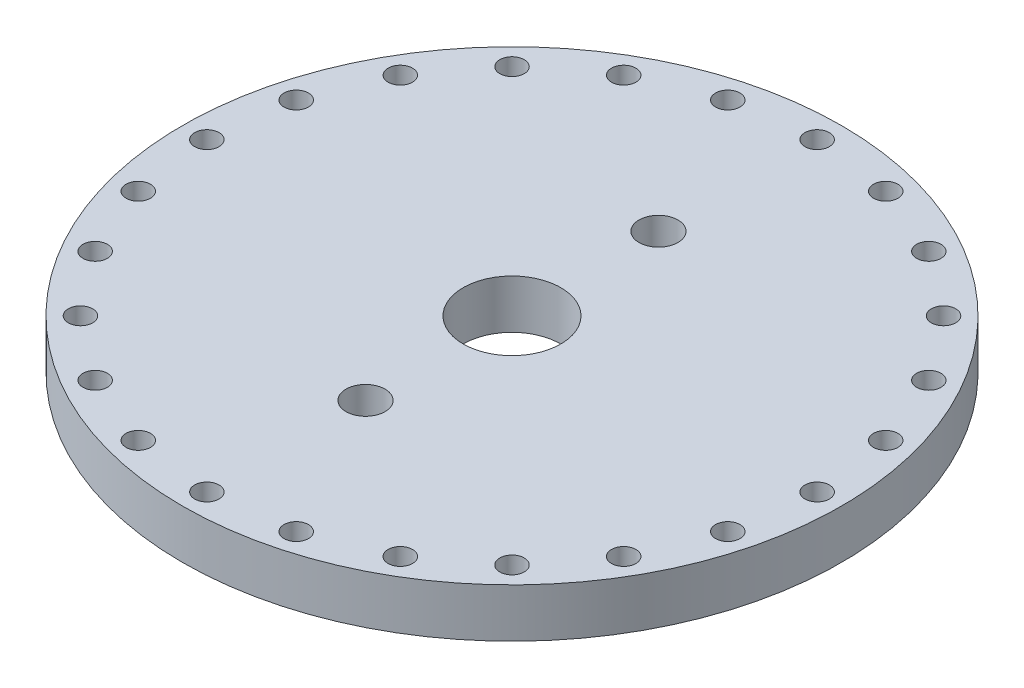
SolidWorks part; units mm, degrees
material "Brass"
ref_plane "Front Plane" through (0, 0, 0) normal (0, 0, 1) x (1, 0, 0)
ref_plane "Top Plane" through (0, 0, 0) normal (0, 1, 0) x (1, 0, 0)
ref_plane "Right Plane" through (0, 0, 0) normal (1, 0, 0) x (0, 0, -1)
sketch "Sketch5" plane through (0, 0, 0) normal (0, 1, 0) x (1, 0, 0)
  line L0 (87.3464, 51.4964) -> (89.0397, 50.8872)
  line L1 (89.0397, 50.8872) -> (90.7249, 50.062)
  line L2 (90.7249, 50.062) -> (90.7249, 49.095)
  line L3 (90.7249, 49.095) -> (89.0397, 48.2698)
  line L4 (89.0397, 48.2698) -> (87.3464, 47.6606)
  line L5 (87.3464, 47.6606) -> (87.2693, 46.4828)
  line L6 (87.2693, 46.4828) -> (88.8685, 45.6578)
  line L7 (88.8685, 45.6578) -> (90.4317, 44.6196)
  line L8 (90.4317, 44.6196) -> (90.3054, 43.6609)
  line L9 (90.3054, 43.6609) -> (88.5268, 43.0627)
  line L10 (88.5268, 43.0627) -> (86.7686, 42.6797)
  line L11 (86.7686, 42.6797) -> (86.5383, 41.5221)
  line L12 (86.5383, 41.5221) -> (88.0162, 40.4955)
  line L13 (88.0162, 40.4955) -> (89.4304, 39.2621)
  line L14 (89.4304, 39.2621) -> (89.1801, 38.328)
  line L15 (89.1801, 38.328) -> (87.3386, 37.9672)
  line L16 (87.3386, 37.9672) -> (85.5454, 37.8169)
  line L17 (85.5454, 37.8169) -> (85.1661, 36.6994)
  line L18 (85.1661, 36.6994) -> (86.4974, 35.4884)
  line L19 (86.4974, 35.4884) -> (87.7385, 34.0811)
  line L20 (87.7385, 34.0811) -> (87.3685, 33.1877)
  line L21 (87.3685, 33.1877) -> (85.4956, 33.0702)
  line L22 (85.4956, 33.0702) -> (83.6981, 33.1553)
  line L23 (83.6981, 33.1553) -> (83.1762, 32.0968)
  line L24 (83.1762, 32.0968) -> (84.3379, 30.7226)
  line L25 (84.3379, 30.7226) -> (85.3848, 29.1653)
  line L26 (85.3848, 29.1653) -> (84.9013, 28.3278)
  line L27 (84.9013, 28.3278) -> (83.0292, 28.4557)
  line L28 (83.0292, 28.4557) -> (81.2581, 28.7747)
  line L29 (81.2581, 28.7747) -> (80.6024, 27.7935)
  line L30 (80.6024, 27.7935) -> (81.575, 26.2794)
  line L31 (81.575, 26.2794) -> (82.4096, 24.5987)
  line L32 (82.4096, 24.5987) -> (81.821, 23.8315)
  line L33 (81.821, 23.8315) -> (79.9815, 24.2028)
  line L34 (79.9815, 24.2028) -> (78.2673, 24.7502)
  line L35 (78.2673, 24.7502) -> (77.4891, 23.8628)
  line L36 (77.4891, 23.8628) -> (78.2556, 22.2348)
  line L37 (78.2556, 22.2348) -> (78.8638, 20.4595)
  line L38 (78.8638, 20.4595) -> (78.18, 19.7757)
  line L39 (78.18, 19.7757) -> (76.4047, 20.3839)
  line L40 (76.4047, 20.3839) -> (74.7767, 21.1504)
  line L41 (74.7767, 21.1504) -> (73.8893, 20.3722)
  line L42 (73.8893, 20.3722) -> (74.4368, 18.658)
  line L43 (74.4368, 18.658) -> (74.808, 16.8186)
  line L44 (74.808, 16.8186) -> (74.0408, 16.2299)
  line L45 (74.0408, 16.2299) -> (72.3602, 17.0645)
  line L46 (72.3602, 17.0645) -> (70.846, 18.0371)
  line L47 (70.846, 18.0371) -> (69.8648, 17.3814)
  line L48 (69.8648, 17.3814) -> (70.1838, 15.6104)
  line L49 (70.1838, 15.6104) -> (70.3117, 13.7382)
  line L50 (70.3117, 13.7382) -> (69.4742, 13.2547)
  line L51 (69.4742, 13.2547) -> (67.9169, 14.3016)
  line L52 (67.9169, 14.3016) -> (66.5427, 15.4634)
  line L53 (66.5427, 15.4634) -> (65.4842, 14.9415)
  line L54 (65.4842, 14.9415) -> (65.5693, 13.1439)
  line L55 (65.5693, 13.1439) -> (65.4518, 11.271)
  line L56 (65.4518, 11.271) -> (64.5584, 10.901)
  line L57 (64.5584, 10.901) -> (63.1511, 12.1422)
  line L58 (63.1511, 12.1422) -> (61.9401, 13.4734)
  line L59 (61.9401, 13.4734) -> (60.8226, 13.0941)
  line L60 (60.8226, 13.0941) -> (60.6724, 11.3009)
  line L61 (60.6724, 11.3009) -> (60.3115, 9.4594)
  line L62 (60.3115, 9.4594) -> (59.3774, 9.2091)
  line L63 (59.3774, 9.2091) -> (58.144, 10.6233)
  line L64 (58.144, 10.6233) -> (57.1174, 12.1012)
  line L65 (57.1174, 12.1012) -> (55.9598, 11.8709)
  line L66 (55.9598, 11.8709) -> (55.5768, 10.1127)
  line L67 (55.5768, 10.1127) -> (54.9786, 8.3341)
  line L68 (54.9786, 8.3341) -> (54.0199, 8.2078)
  line L69 (54.0199, 8.2078) -> (52.9817, 9.771)
  line L70 (52.9817, 9.771) -> (52.1567, 11.3702)
  line L71 (52.1567, 11.3702) -> (50.979, 11.2931)
  line L72 (50.979, 11.2931) -> (50.3698, 9.5998)
  line L73 (50.3698, 9.5998) -> (49.5446, 7.9146)
  line L74 (49.5446, 7.9146) -> (48.5775, 7.9146)
  line L75 (48.5775, 7.9146) -> (47.7523, 9.5998)
  line L76 (47.7523, 9.5998) -> (47.1431, 11.2931)
  line L77 (47.1431, 11.2931) -> (45.9654, 11.3702)
  line L78 (45.9654, 11.3702) -> (45.1403, 9.771)
  line L79 (45.1403, 9.771) -> (44.1021, 8.2078)
  line L80 (44.1021, 8.2078) -> (43.1434, 8.3341)
  line L81 (43.1434, 8.3341) -> (42.5452, 10.1127)
  line L82 (42.5452, 10.1127) -> (42.1622, 11.8709)
  line L83 (42.1622, 11.8709) -> (41.0046, 12.1012)
  line L84 (41.0046, 12.1012) -> (39.978, 10.6233)
  line L85 (39.978, 10.6233) -> (38.7447, 9.2091)
  line L86 (38.7447, 9.2091) -> (37.8106, 9.4594)
  line L87 (37.8106, 9.4594) -> (37.4497, 11.3009)
  line L88 (37.4497, 11.3009) -> (37.2994, 13.0941)
  line L89 (37.2994, 13.0941) -> (36.1819, 13.4734)
  line L90 (36.1819, 13.4734) -> (34.9709, 12.1422)
  line L91 (34.9709, 12.1422) -> (33.5636, 10.901)
  line L92 (33.5636, 10.901) -> (32.6702, 11.271)
  line L93 (32.6702, 11.271) -> (32.5527, 13.1439)
  line L94 (32.5527, 13.1439) -> (32.6378, 14.9415)
  line L95 (32.6378, 14.9415) -> (31.5793, 15.4634)
  line L96 (31.5793, 15.4634) -> (30.2051, 14.3016)
  line L97 (30.2051, 14.3016) -> (28.6478, 13.2547)
  line L98 (28.6478, 13.2547) -> (27.8103, 13.7382)
  line L99 (27.8103, 13.7382) -> (27.9382, 15.6104)
  line L100 (27.9382, 15.6104) -> (28.2572, 17.3814)
  line L101 (28.2572, 17.3814) -> (27.276, 18.0371)
  line L102 (27.276, 18.0371) -> (25.7619, 17.0645)
  line L103 (25.7619, 17.0645) -> (24.0812, 16.2299)
  line L104 (24.0812, 16.2299) -> (23.314, 16.8186)
  line L105 (23.314, 16.8186) -> (23.6853, 18.658)
  line L106 (23.6853, 18.658) -> (24.2327, 20.3722)
  line L107 (24.2327, 20.3722) -> (23.3453, 21.1504)
  line L108 (23.3453, 21.1504) -> (21.7173, 20.3839)
  line L109 (21.7173, 20.3839) -> (19.9421, 19.7757)
  line L110 (19.9421, 19.7757) -> (19.2582, 20.4595)
  line L111 (19.2582, 20.4595) -> (19.8664, 22.2348)
  line L112 (19.8664, 22.2348) -> (20.6329, 23.8628)
  line L113 (20.6329, 23.8628) -> (19.8547, 24.7502)
  line L114 (19.8547, 24.7502) -> (18.1405, 24.2028)
  line L115 (18.1405, 24.2028) -> (16.3011, 23.8315)
  line L116 (16.3011, 23.8315) -> (15.7124, 24.5987)
  line L117 (15.7124, 24.5987) -> (16.547, 26.2794)
  line L118 (16.547, 26.2794) -> (17.5196, 27.7935)
  line L119 (17.5196, 27.7935) -> (16.8639, 28.7747)
  line L120 (16.8639, 28.7747) -> (15.0929, 28.4557)
  line L121 (15.0929, 28.4557) -> (13.2207, 28.3278)
  line L122 (13.2207, 28.3278) -> (12.7372, 29.1653)
  line L123 (12.7372, 29.1653) -> (13.7841, 30.7226)
  line L124 (13.7841, 30.7226) -> (14.9459, 32.0968)
  line L125 (14.9459, 32.0968) -> (14.424, 33.1553)
  line L126 (14.424, 33.1553) -> (12.6264, 33.0702)
  line L127 (12.6264, 33.0702) -> (10.7535, 33.1877)
  line L128 (10.7535, 33.1877) -> (10.3835, 34.0811)
  line L129 (10.3835, 34.0811) -> (11.6247, 35.4884)
  line L130 (11.6247, 35.4884) -> (12.9559, 36.6994)
  line L131 (12.9559, 36.6994) -> (12.5766, 37.8169)
  line L132 (12.5766, 37.8169) -> (10.7834, 37.9672)
  line L133 (10.7834, 37.9672) -> (8.9419, 38.328)
  line L134 (8.9419, 38.328) -> (8.6916, 39.2621)
  line L135 (8.6916, 39.2621) -> (10.1058, 40.4955)
  line L136 (10.1058, 40.4955) -> (11.5837, 41.5221)
  line L137 (11.5837, 41.5221) -> (11.3534, 42.6797)
  line L138 (11.3534, 42.6797) -> (9.5952, 43.0627)
  line L139 (9.5952, 43.0627) -> (7.8167, 43.6609)
  line L140 (7.8167, 43.6609) -> (7.6903, 44.6196)
  line L141 (7.6903, 44.6196) -> (9.2536, 45.6578)
  line L142 (9.2536, 45.6578) -> (10.8528, 46.4828)
  line L143 (10.8528, 46.4828) -> (10.7757, 47.6606)
  line L144 (10.7757, 47.6606) -> (9.0823, 48.2698)
  line L145 (9.0823, 48.2698) -> (7.3971, 49.095)
  line L146 (7.3971, 49.095) -> (7.3971, 50.062)
  line L147 (7.3971, 50.062) -> (9.0823, 50.8872)
  line L148 (9.0823, 50.8872) -> (10.7757, 51.4964)
  line L149 (10.7757, 51.4964) -> (10.8528, 52.6742)
  line L150 (10.8528, 52.6742) -> (9.2536, 53.4992)
  line L151 (9.2536, 53.4992) -> (7.6903, 54.5374)
  line L152 (7.6903, 54.5374) -> (7.8167, 55.4961)
  line L153 (7.8167, 55.4961) -> (9.5952, 56.0943)
  line L154 (9.5952, 56.0943) -> (11.3534, 56.4773)
  line L155 (11.3534, 56.4773) -> (11.5837, 57.6349)
  line L156 (11.5837, 57.6349) -> (10.1058, 58.6615)
  line L157 (10.1058, 58.6615) -> (8.6916, 59.8949)
  line L158 (8.6916, 59.8949) -> (8.9419, 60.829)
  line L159 (8.9419, 60.829) -> (10.7834, 61.1898)
  line L160 (10.7834, 61.1898) -> (12.5766, 61.3401)
  line L161 (12.5766, 61.3401) -> (12.9559, 62.4576)
  line L162 (12.9559, 62.4576) -> (11.6247, 63.6686)
  line L163 (11.6247, 63.6686) -> (10.3835, 65.0759)
  line L164 (10.3835, 65.0759) -> (10.7535, 65.9693)
  line L165 (10.7535, 65.9693) -> (12.6264, 66.0868)
  line L166 (12.6264, 66.0868) -> (14.424, 66.0017)
  line L167 (14.424, 66.0017) -> (14.9459, 67.0602)
  line L168 (14.9459, 67.0602) -> (13.7841, 68.4344)
  line L169 (13.7841, 68.4344) -> (12.7372, 69.9917)
  line L170 (12.7372, 69.9917) -> (13.2207, 70.8292)
  line L171 (13.2207, 70.8292) -> (15.0929, 70.7013)
  line L172 (15.0929, 70.7013) -> (16.8639, 70.3823)
  line L173 (16.8639, 70.3823) -> (17.5196, 71.3635)
  line L174 (17.5196, 71.3635) -> (16.547, 72.8776)
  line L175 (16.547, 72.8776) -> (15.7124, 74.5583)
  line L176 (15.7124, 74.5583) -> (16.3011, 75.3255)
  line L177 (16.3011, 75.3255) -> (18.1405, 74.9542)
  line L178 (18.1405, 74.9542) -> (19.8547, 74.4068)
  line L179 (19.8547, 74.4068) -> (20.6329, 75.2942)
  line L180 (20.6329, 75.2942) -> (19.8664, 76.9222)
  line L181 (19.8664, 76.9222) -> (19.2582, 78.6975)
  line L182 (19.2582, 78.6975) -> (19.9421, 79.3813)
  line L183 (19.9421, 79.3813) -> (21.7173, 78.7731)
  line L184 (21.7173, 78.7731) -> (23.3453, 78.0066)
  line L185 (23.3453, 78.0066) -> (24.2327, 78.7848)
  line L186 (24.2327, 78.7848) -> (23.6853, 80.499)
  line L187 (23.6853, 80.499) -> (23.314, 82.3384)
  line L188 (23.314, 82.3384) -> (24.0812, 82.9271)
  line L189 (24.0812, 82.9271) -> (25.7619, 82.0925)
  line L190 (25.7619, 82.0925) -> (27.276, 81.1199)
  line L191 (27.276, 81.1199) -> (28.2572, 81.7756)
  line L192 (28.2572, 81.7756) -> (27.9382, 83.5466)
  line L193 (27.9382, 83.5466) -> (27.8103, 85.4188)
  line L194 (27.8103, 85.4188) -> (28.6478, 85.9023)
  line L195 (28.6478, 85.9023) -> (30.2051, 84.8554)
  line L196 (30.2051, 84.8554) -> (31.5793, 83.6936)
  line L197 (31.5793, 83.6936) -> (32.6378, 84.2155)
  line L198 (32.6378, 84.2155) -> (32.5527, 86.0131)
  line L199 (32.5527, 86.0131) -> (32.6702, 87.886)
  line L200 (32.6702, 87.886) -> (33.5636, 88.256)
  line L201 (33.5636, 88.256) -> (34.9709, 87.0148)
  line L202 (34.9709, 87.0148) -> (36.1819, 85.6836)
  line L203 (36.1819, 85.6836) -> (37.2994, 86.0629)
  line L204 (37.2994, 86.0629) -> (37.4497, 87.8561)
  line L205 (37.4497, 87.8561) -> (37.8106, 89.6976)
  line L206 (37.8106, 89.6976) -> (38.7447, 89.9479)
  line L207 (38.7447, 89.9479) -> (39.978, 88.5337)
  line L208 (39.978, 88.5337) -> (41.0046, 87.0558)
  line L209 (41.0046, 87.0558) -> (42.1622, 87.2861)
  line L210 (42.1622, 87.2861) -> (42.5452, 89.0443)
  line L211 (42.5452, 89.0443) -> (43.1434, 90.8228)
  line L212 (43.1434, 90.8228) -> (44.1021, 90.9492)
  line L213 (44.1021, 90.9492) -> (45.1403, 89.386)
  line L214 (45.1403, 89.386) -> (45.9654, 87.7868)
  line L215 (45.9654, 87.7868) -> (47.1431, 87.8639)
  line L216 (47.1431, 87.8639) -> (47.7523, 89.5572)
  line L217 (47.7523, 89.5572) -> (48.5775, 91.2424)
  line L218 (48.5775, 91.2424) -> (49.5446, 91.2424)
  line L219 (49.5446, 91.2424) -> (50.3698, 89.5572)
  line L220 (50.3698, 89.5572) -> (50.979, 87.8639)
  line L221 (50.979, 87.8639) -> (52.1567, 87.7868)
  line L222 (52.1567, 87.7868) -> (52.9817, 89.386)
  line L223 (52.9817, 89.386) -> (54.0199, 90.9492)
  line L224 (54.0199, 90.9492) -> (54.9786, 90.8228)
  line L225 (54.9786, 90.8228) -> (55.5768, 89.0443)
  line L226 (55.5768, 89.0443) -> (55.9598, 87.2861)
  line L227 (55.9598, 87.2861) -> (57.1174, 87.0558)
  line L228 (57.1174, 87.0558) -> (58.144, 88.5337)
  line L229 (58.144, 88.5337) -> (59.3774, 89.9479)
  line L230 (59.3774, 89.9479) -> (60.3115, 89.6976)
  line L231 (60.3115, 89.6976) -> (60.6724, 87.8561)
  line L232 (60.6724, 87.8561) -> (60.8226, 86.0629)
  line L233 (60.8226, 86.0629) -> (61.9401, 85.6836)
  line L234 (61.9401, 85.6836) -> (63.1511, 87.0148)
  line L235 (63.1511, 87.0148) -> (64.5584, 88.256)
  line L236 (64.5584, 88.256) -> (65.4518, 87.886)
  line L237 (65.4518, 87.886) -> (65.5693, 86.0131)
  line L238 (65.5693, 86.0131) -> (65.4842, 84.2155)
  line L239 (65.4842, 84.2155) -> (66.5427, 83.6936)
  line L240 (66.5427, 83.6936) -> (67.9169, 84.8554)
  line L241 (67.9169, 84.8554) -> (69.4742, 85.9023)
  line L242 (69.4742, 85.9023) -> (70.3117, 85.4188)
  line L243 (70.3117, 85.4188) -> (70.1838, 83.5466)
  line L244 (70.1838, 83.5466) -> (69.8648, 81.7756)
  line L245 (69.8648, 81.7756) -> (70.846, 81.1199)
  line L246 (70.846, 81.1199) -> (72.3602, 82.0925)
  line L247 (72.3602, 82.0925) -> (74.0408, 82.9271)
  line L248 (74.0408, 82.9271) -> (74.808, 82.3384)
  line L249 (74.808, 82.3384) -> (74.4368, 80.499)
  line L250 (74.4368, 80.499) -> (73.8893, 78.7848)
  line L251 (73.8893, 78.7848) -> (74.7767, 78.0066)
  line L252 (74.7767, 78.0066) -> (76.4047, 78.7731)
  line L253 (76.4047, 78.7731) -> (78.18, 79.3813)
  line L254 (78.18, 79.3813) -> (78.8638, 78.6975)
  line L255 (78.8638, 78.6975) -> (78.2556, 76.9222)
  line L256 (78.2556, 76.9222) -> (77.4891, 75.2942)
  line L257 (77.4891, 75.2942) -> (78.2673, 74.4068)
  line L258 (78.2673, 74.4068) -> (79.9815, 74.9542)
  line L259 (79.9815, 74.9542) -> (81.821, 75.3255)
  line L260 (81.821, 75.3255) -> (82.4096, 74.5583)
  line L261 (82.4096, 74.5583) -> (81.575, 72.8776)
  line L262 (81.575, 72.8776) -> (80.6024, 71.3635)
  line L263 (80.6024, 71.3635) -> (81.2581, 70.3823)
  line L264 (81.2581, 70.3823) -> (83.0292, 70.7013)
  line L265 (83.0292, 70.7013) -> (84.9013, 70.8292)
  line L266 (84.9013, 70.8292) -> (85.3848, 69.9917)
  line L267 (85.3848, 69.9917) -> (84.3379, 68.4344)
  line L268 (84.3379, 68.4344) -> (83.1762, 67.0602)
  line L269 (83.1762, 67.0602) -> (83.6981, 66.0017)
  line L270 (83.6981, 66.0017) -> (85.4956, 66.0868)
  line L271 (85.4956, 66.0868) -> (87.3685, 65.9693)
  line L272 (87.3685, 65.9693) -> (87.7385, 65.0759)
  line L273 (87.7385, 65.0759) -> (86.4974, 63.6686)
  line L274 (86.4974, 63.6686) -> (85.1661, 62.4576)
  line L275 (85.1661, 62.4576) -> (85.5454, 61.3401)
  line L276 (85.5454, 61.3401) -> (87.3386, 61.1898)
  line L277 (87.3386, 61.1898) -> (89.1801, 60.829)
  line L278 (89.1801, 60.829) -> (89.4304, 59.8949)
  line L279 (89.4304, 59.8949) -> (88.0162, 58.6615)
  line L280 (88.0162, 58.6615) -> (86.5383, 57.6349)
  line L281 (86.5383, 57.6349) -> (86.7686, 56.4773)
  line L282 (86.7686, 56.4773) -> (88.5268, 56.0943)
  line L283 (88.5268, 56.0943) -> (90.3054, 55.4961)
  line L284 (90.3054, 55.4961) -> (90.4317, 54.5374)
  line L285 (90.4317, 54.5374) -> (88.8685, 53.4992)
  line L286 (88.8685, 53.4992) -> (87.2693, 52.6742)
  line L287 (87.2693, 52.6742) -> (87.3464, 51.4964)
  line L288 (49.061, 91.2424) -> (49.061, 7.9146) construction
  line L289 (7.3971, 49.5785) -> (90.7249, 49.5785) construction
  point P292 (49.061, 49.5785)
sketch "Sketch6" plane through (0, 0, 0) normal (0, 1, 0) x (1, 0, 0)
  line L0 (49.061, 91.2424) -> (49.061, 7.9146) construction
  circle A0 centre (49.061, 49.5785) radius 4
  dimension "D1" = 8
sketch "Sketch7" plane through (0, 0, 0) normal (0, 1, 0) x (1, 0, 0)
  line L0 (49.061, 91.2424) -> (49.061, 7.9146) construction
  line L1 (25.4921, 49.5785) -> (64.6594, 49.5785) construction
  line L2 (7.3971, 49.5785) -> (90.7249, 49.5785) construction
  circle A0 centre (49.061, 61.5785) radius 1.6
  circle A1 centre (49.061, 37.5785) radius 1.6
  dimension "D2" = 3.2
  dimension "D1" = 12
sketch "Sketch8" plane through (0, 0, 0) normal (0, 1, 0) x (1, 0, 0)
  line L0 (7.3971, 49.5785) -> (90.7249, 49.5785) construction
  circle A0 centre (49.061, 49.5785) radius 27
  dimension "D1" = 54
sketch "Sketch9" plane through (0, 0, 0) normal (0, 1, 0) x (1, 0, 0)
  line L0 (49.061, 91.2424) -> (49.061, 7.9146) construction
  line L1 (49.061, 74.5785) -> (49.061, 76.5785) construction
  circle A0 centre (49.061, 74.5785) radius 1
  circle A1 centre (49.061, 49.5785) radius 27 construction
  circle A2 centre (55.5315, 73.7266) radius 1
  circle A3 centre (61.561, 71.2291) radius 1
  circle A4 centre (66.7387, 67.2562) radius 1
  circle A5 centre (70.7116, 62.0785) radius 1
  circle A6 centre (73.2092, 56.049) radius 1
  circle A7 centre (74.061, 49.5785) radius 1
  circle A8 centre (73.2092, 43.108) radius 1
  circle A9 centre (70.7116, 37.0785) radius 1
  circle A10 centre (66.7387, 31.9008) radius 1
  circle A11 centre (61.561, 27.9279) radius 1
  circle A12 centre (55.5315, 25.4304) radius 1
  circle A13 centre (49.061, 24.5785) radius 1
  circle A14 centre (42.5905, 25.4304) radius 1
  circle A15 centre (36.561, 27.9279) radius 1
  circle A16 centre (31.3833, 31.9008) radius 1
  circle A17 centre (27.4104, 37.0785) radius 1
  circle A18 centre (24.9129, 43.108) radius 1
  circle A19 centre (24.061, 49.5785) radius 1
  circle A20 centre (24.9129, 56.049) radius 1
  circle A21 centre (27.4104, 62.0785) radius 1
  circle A22 centre (31.3833, 67.2562) radius 1
  circle A23 centre (36.561, 71.2291) radius 1
  circle A24 centre (42.5905, 73.7266) radius 1
  point P55 (49.061, 49.5785)
  dimension "D1" = 2
  dimension "D2" = 2
  dimension "D3" = 24
extrude "Boss-Extrude1" add sketch "Sketch8" along normal blind 4
extrude "Boss-Extrude2" [suppressed] add sketch "Sketch5" along normal up to surface (4 mm away) up to face at (49.061, 4, -22.5785)
extrude "Cut-Extrude1" cut sketch "Sketch6" along normal up to next
extrude "Cut-Extrude2" cut sketch "Sketch7" along normal up to next
extrude "Cut-Extrude3" cut sketch "Sketch9" along normal up to next
ref_axis "Axis1" [suppressed] through (49.061, 4, -49.5785) along (0, -1, 0)
sketch "Sketch11" plane through (0, 0, 0) normal (0, 1, 0) x (1, 0, 0)
  line L0 (59.3935, 74.5232) -> (49.061, 49.5785) construction
  line L1 (49.061, 49.5785) -> (49.061, 76.5785) construction
  circle A0 centre (49.061, 49.5785) radius 27 construction
  circle A1 centre (54.8013, 63.4367) radius 1.25
  circle A2 centre (62.9192, 55.3188) radius 1.25
  circle A3 centre (62.9192, 43.8382) radius 1.25
  circle A4 centre (54.8013, 35.7203) radius 1.25
  circle A5 centre (43.3208, 35.7203) radius 1.25
  circle A6 centre (35.2028, 43.8382) radius 1.25
  circle A7 centre (35.2028, 55.3188) radius 1.25
  circle A8 centre (43.3208, 63.4367) radius 1.25
  point P0 (49.061, 49.5785)
  point P36 (49.061, 49.5785)
  dimension "D2" = 2.5
  dimension "D1" = 15
  dimension "D4" = 22.5
  dimension "D3" = 8
extrude "Cut-Extrude4" [suppressed] cut sketch "Sketch11" along normal up to next
